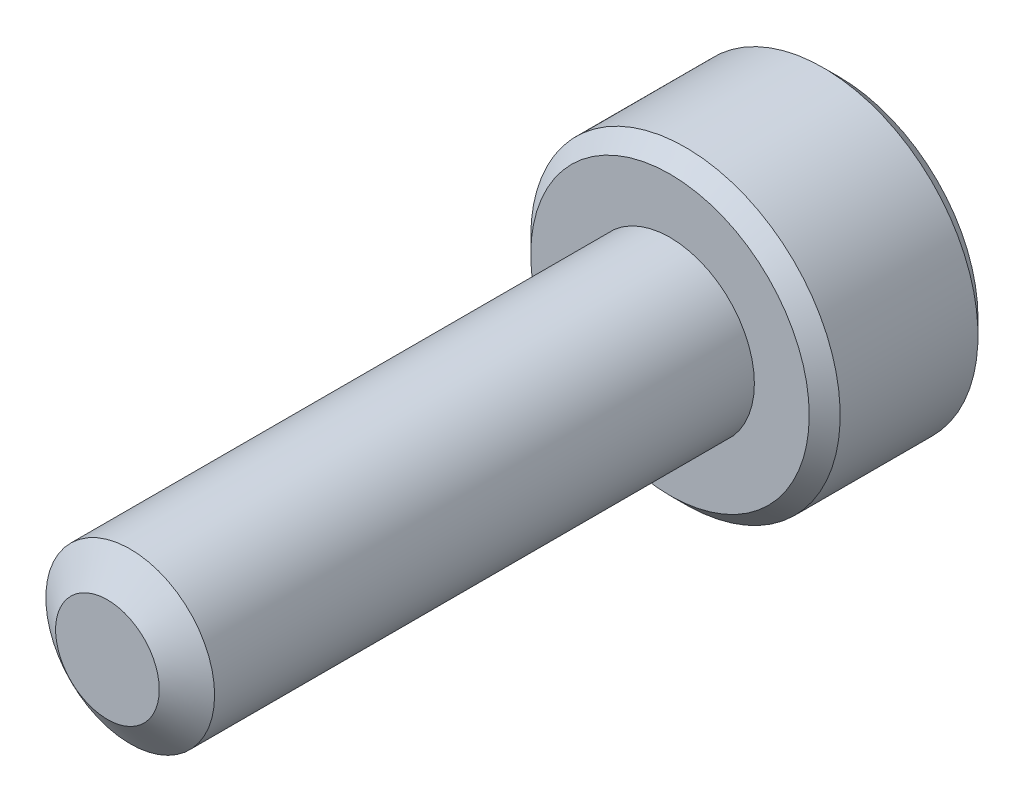
SolidWorks part; units mm, degrees
other "DetailItem1"
material "AISI 304"
ref_plane "Front Plane" through (0, 0, 0) normal (0, 0, 1) x (1, 0, 0)
ref_plane "Top Plane" through (0, 0, 0) normal (0, 1, 0) x (1, 0, 0)
ref_plane "Right Plane" through (0, 0, 0) normal (1, 0, 0) x (0, 0, -1)
sketch "Sketch1" plane through (0, 0, 0) normal (0, 0, 1) x (1, 0, 0)
  circle A0 centre (0, 0) radius 1.5
  dimension "OD" = 3
extrude "Extrude1" add sketch "Sketch1" against normal blind 10
sketch "Sketch2" plane through (0, 0, 0) normal (0, 0, 1) x (1, 0, 0)
  circle A0 centre (0, 0) radius 1.5 construction
  circle A1 centre (0, 0) radius 1.5
curve "Helix/Spiral1" [suppressed] pitch 0.5 height 10.5 turns 21 parameters "pitch"=0.5
sketch "Sketch3" plane through (0, 0, 0) normal (1, 0, 0) x (0, 0, -1)
  line L0 (-0.4375, 1.5) -> (-0.25, 1.1752)
  line L1 (-0.25, 1.1752) -> (-0.1875, 1.1752)
  line L2 (-0.1875, 1.1752) -> (0, 1.5)
  line L3 (-0.4375, 1.5) -> (0, 1.5)
  line L4 (-0.2187, 1.5) -> (-0.2188, 1.1752) construction
  line L5 (-0.3438, 1.3376) -> (-0.0938, 1.3376) construction
  line L6 (0, 1.5) -> (0, -1.5) construction
  dimension "D1" = 0.0625
  dimension "D2" = 0.25
  dimension "D3" = 60
sweep "Cut-Sweep1" [suppressed] cut profiles "Sketch3" path "Helix/Spiral1"
sketch "Sketch4" plane through (0, 0, 0) normal (1, 0, 0) x (0, 0, -1)
  line L0 (0.4053, 1.5) -> (0, 0.9212)
  line L1 (0, 0.9212) -> (0, 1.5)
  line L2 (0.4053, 1.5) -> (0, 1.5)
  line L3 (-0.4375, 1.5) -> (0, 1.5) construction
  line L4 (0, 0) -> (7.0209, 0) construction
  dimension "D1" = 55
  dimension "D2" = 0.254
revolve "Cut-Revolve1" cut sketch "Sketch4" angle 360 about L4
sketch "Sketch6" plane through (0, 0, -10) normal (0, 0, -1) x (-1, 0, 0)
  circle A0 centre (0, 0) radius 2.75
  dimension "head dia" = 5.5
extrude "Extrude2" add sketch "Sketch6" along normal blind 3
sketch "Sketch7" plane through (0, 0, -13) normal (0, 0, -1) x (-1, 0, 0)
  line L1 (0, 1.4434) -> (-1.25, 0.7217)
  line L2 (-1.25, 0.7217) -> (-1.25, -0.7217)
  line L3 (-1.25, -0.7217) -> (0, -1.4434)
  line L4 (0, -1.4434) -> (1.25, -0.7217)
  line L5 (1.25, -0.7217) -> (1.25, 0.7217)
  line L6 (1.25, 0.7217) -> (0, 1.4434)
  circle A0 centre (0, 0) radius 1.25 construction
  dimension "hex dia" = 2.5
extrude "Cut-Extrude1" cut sketch "Sketch7" against normal blind 1.875
sketch "Sketch8" plane through (0, 0, -13) normal (0, 0, -1) x (-1, 0, 0)
  circle A0 centre (0, 0) radius 1.4434
extrude "Cut-Extrude2" cut sketch "Sketch8" against normal through all draft 45
chamfer "Chamfer1" distance 0.275 angle 45 2 edges at (-2.75, 0, -13) (-2.75, 0, -10)
sketch "Sketch10" plane through (0, 0, -10) normal (0, 0, 1) x (1, 0, 0)
  circle A1 centre (0, 0) radius 1.5
  circle A2 centre (0, 0) radius 1.5
  dimension "D1" = 0
ref_plane "Plane1" through (0, 0, 0) normal (0, 0, 1) x (1, 0, 0)
extrude "partial thread" [suppressed] add sketch "Sketch10" along normal up to surface (4 mm away) separate body up to plane "Plane1"
chamfer "Chamfer2" [suppressed] distance 0.06 angle 45
combine bodies "Combine1" [suppressed] operation type add bodies to combine 107 108
sketch "Sketch9" plane through (0, 0, 0) normal (1, 0, 0) x (0, 0, -1)
  line L0 (0, 1.5) -> (0, -1.5) construction
  line L1 (1.25, 1.5) -> (1.25, -1.5) construction
  dimension "D1" = 1.25
equation "\"D3@Helix/Spiral1\" = \"screw length@Extrude1\"+\"pitch@Helix/Spiral1\""
equation "\"D1@Sketch3\" = \"pitch@Helix/Spiral1\"*.125"
equation "\"D2@Sketch3\" = \"pitch@Helix/Spiral1\"*.5"
equation "\"D1@Cut-Extrude1\" = \"hex dia@Sketch7\"*.75"
equation "\"D1@Chamfer1\" = \"head dia@Sketch6\"*.05"
equation "\"D1@Sketch9\" = \"pitch@Helix/Spiral1\"*2.5"
equation "\"D1@Chamfer2\"=\"OD@Sketch1\"*.02"
